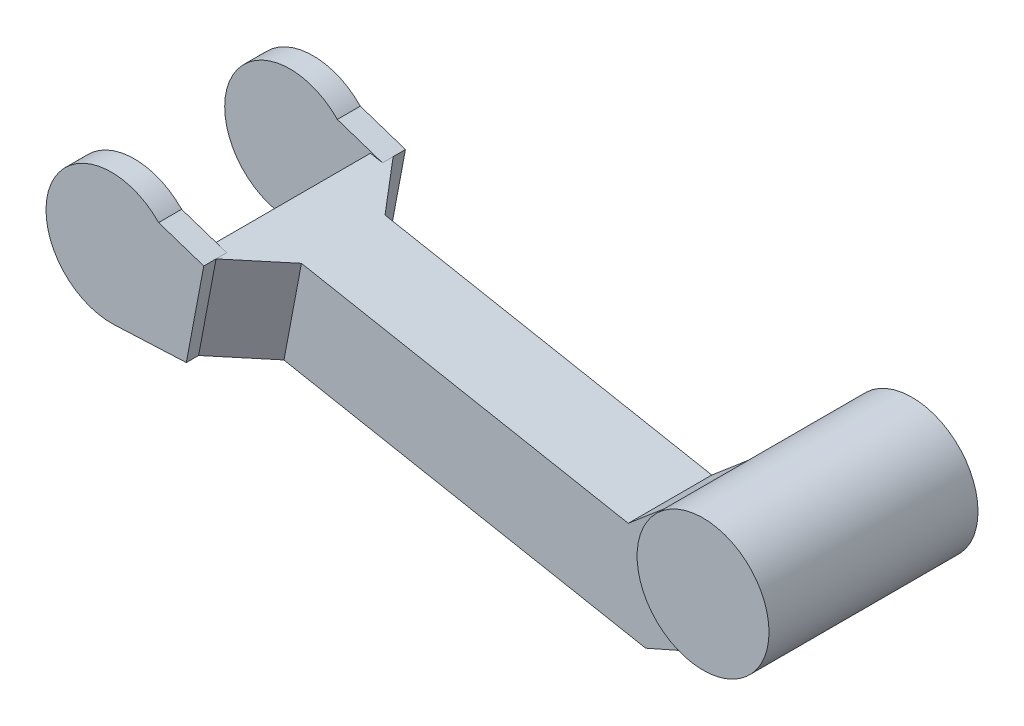
SolidWorks part; units mm, degrees
ref_plane "Front Plane" through (0, 0, 0) normal (0, 0, 1) x (1, 0, 0)
ref_plane "Top Plane" through (0, 0, 0) normal (0, 1, 0) x (1, 0, 0)
ref_plane "Right Plane" through (0, 0, 0) normal (1, 0, 0) x (0, 0, -1)
sketch "Sketch1" plane through (0, 0, 0) normal (0, 0, 1) x (1, 0, 0)
  circle A0 centre (0.2851, 0) radius 0.0316
extrude "Boss-Extrude1" add sketch "Sketch1" along normal blind 0.05 and the other way blind 0.05
sketch "Sketch2" plane through (0, 0, 0) normal (0, 0, 1) x (1, 0, 0)
  line L0 (0.2563, 0.0129) -> (0.2193, -0.0186)
  line L1 (0.2193, -0.0186) -> (0.039, 0.0155)
  line L2 (0.039, 0.0155) -> (0.0294, -0.0285)
  line L3 (0.0294, -0.0285) -> (0.2276, -0.0662)
  line L4 (0.2276, -0.0662) -> (0.2899, -0.0386)
  line L5 (0.2899, -0.0386) -> (0.3052, -0.0243)
  line L6 (0.3052, -0.0243) -> (0.2563, 0.0129)
  circle A0 centre (0.2851, 0) radius 0.0316 construction
  point P11 (0.0282, 0.0172)
  point P12 (0.0282, 0.0172)
  point P13 (0, 0)
  point P14 (0.0412, 0.0154)
  point P15 (0, 0)
  point P16 (0, 0)
  point P17 (0.039, 0.0155)
  point P18 (0.0294, -0.0285)
extrude "Boss-Extrude2" add sketch "Sketch2" along normal blind 0.02 and the other way blind 0.02
sketch "Sketch4" plane through (0.0042, 0.0221, 0) normal (0.1857, 0.9826, 0) x (0.9826, -0.1857, 0)
  line L0 (0.0349, 0.0426) -> (0.0349, -0.0421)
  line L1 (0.0349, -0.0421) -> (0.0407, -0.0421)
  line L2 (0.0407, -0.0421) -> (0.0598, -0.02)
  line L3 (0.2189, -0.02) -> (0.0354, -0.02) construction
  line L4 (0.0598, -0.02) -> (0.0598, 0.02)
  line L5 (0.2189, 0.02) -> (0.0354, 0.02) construction
  line L6 (0.0598, 0.02) -> (0.0407, 0.0426)
  line L7 (0.0407, 0.0426) -> (0.0349, 0.0426)
extrude "Boss-Extrude3" add sketch "Sketch4" against normal blind 0.045
sketch "Sketch5" plane through (0, 0, 0) normal (0, 0, 1) x (1, 0, 0)
  line L0 (0.0014, -0.0313) -> (0.0358, -0.0297)
  line L1 (0.0358, -0.0297) -> (0.0442, 0.0145)
  line L2 (0.0442, 0.0145) -> (0.0226, 0.0217)
  arc A0 (0.0226, 0.0217) -> (0.0014, -0.0313) centre (0, 0) ccw
extrude "Boss-Extrude4" add sketch "Sketch5" along normal blind 0.011 from offset 0.037
extrude "Boss-Extrude5" add sketch "Sketch5<2>" against normal blind 0.011 from offset 0.0375 offset against normal yes
sketch "Sketch5<2>" plane through (0, 0, 0) normal (0, 0, 1) x (1, 0, 0) same geometry as "Sketch5"
